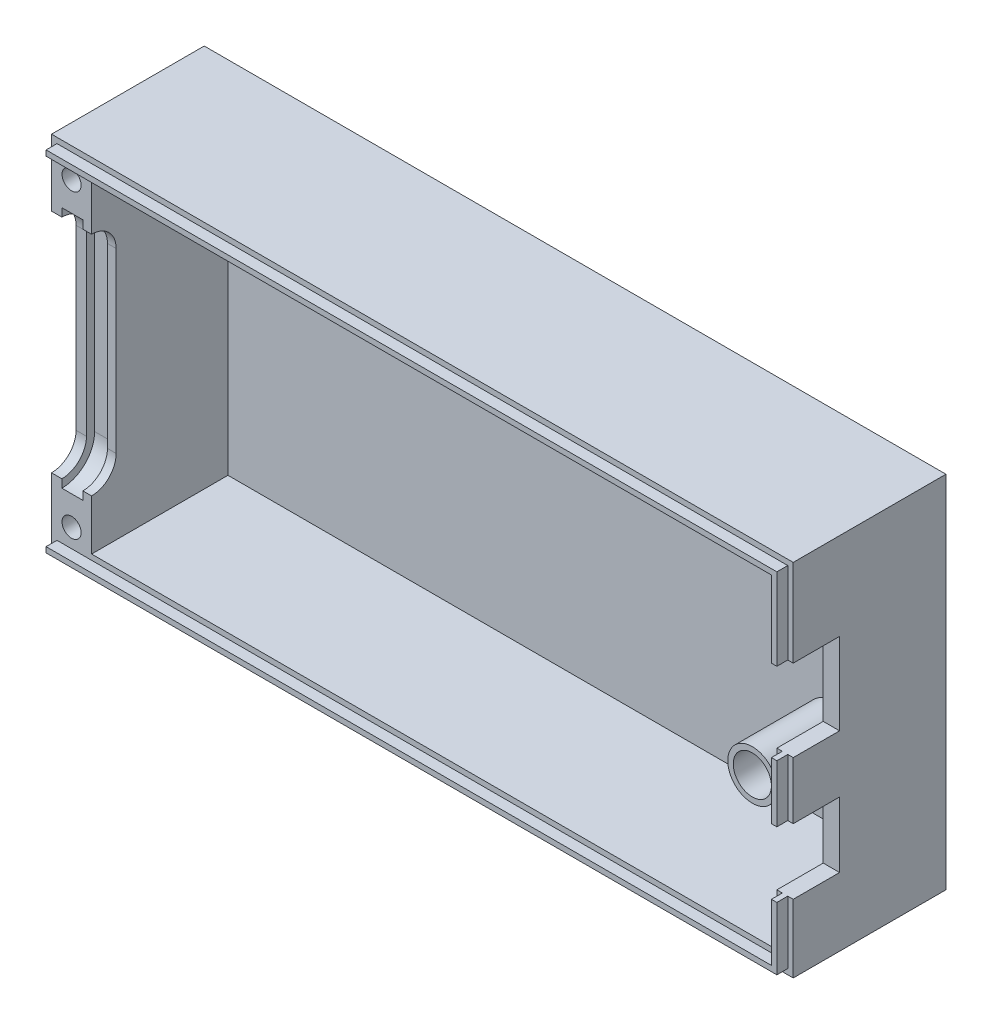
SolidWorks part; units mm, degrees
note: The reader was unsure of these and kept them because the rebuilt part matched: shared geometry of "Szkic8<2>".
ref_plane "Płaszczyzna przednia" through (0, 0, 0) normal (0, 0, 1) x (1, 0, 0)
ref_plane "Płaszczyzna górna" through (0, 0, 0) normal (0, 1, 0) x (1, 0, 0)
ref_plane "Płaszczyzna prawa" through (0, 0, 0) normal (1, 0, 0) x (0, 0, -1)
sketch "Szkic1" plane through (0, 0, 0) normal (0, 0, 1) x (1, 0, 0)
  line L1 (65, -30) -> (-65, -30)
  line L2 (65, -30) -> (65, 30)
  line L3 (65, 30) -> (-65, 30)
  line L4 (-65, -30) -> (-65, 30)
  line L5 (65, -30) -> (-65, 30) construction
  line L6 (65, 30) -> (-65, -30) construction
  point P0 (0, 0)
  dimension "D1" = 130
  dimension "D2" = 60
extrude "Dodanie-wyciągnięcie1" add sketch "Szkic1" along normal blind 25
shell "Skorupa1" thickness 3 removed face at (0, 0, 25) outward yes
sketch "Szkic3" plane through (-65, 0, 0) normal (1, 0, 0) x (0, 0, -1)
  line L4 (0, -30) -> (0, 30)
  line L5 (0, 30) -> (-25, 30)
  line L6 (-25, 30) -> (-25, -30)
  line L7 (-25, -30) -> (0, -30)
  line L8 (0, -30) -> (0, 30)
  line L9 (0, 30) -> (-25, 30)
  line L10 (-25, 30) -> (-25, -30)
  line L11 (-25, -30) -> (0, -30)
  dimension "D1" = 0
extrude "Wytnij-wyciągnięcie1" cut sketch "Szkic3" against normal blind 1.1
sketch "Szkic4" plane through (-66.1, 0, 0) normal (1, 0, 0) x (0, 0, -1)
  line L1 (-25, 30) -> (-25, -30) construction
  line L2 (-25, 30) -> (-25, -30)
  line L4 (-25, 22.175) -> (-25, -22.175)
  line L6 (-19, 16.275) -> (-19, -16.275)
  arc A2 (-19, 16.275) -> (-25, 22.275) centre (-25, 16.275) ccw
  arc A3 (-19, -16.275) -> (-25, -22.275) centre (-25, -16.275) cw
  point P1 (-25, 0)
  point P11 (-19, 0)
  dimension "D2" = 6
  dimension "D3" = 44.35
  dimension "D1" = 6
  dimension "D5" = 6
  dimension "D4" = 32.55
extrude "Dodanie-wyciągnięcie2" add sketch "Szkic4" along normal blind 3.85
sketch "Szkic5" plane through (-62.25, 0, 0) normal (1, 0, 0) x (0, 0, -1)
  line L0 (-20.5, 16.275) -> (-20.5, -16.275)
  line L1 (-25, 22.275) -> (-25, 20.775)
  line L2 (-25, -20.775) -> (-25, -22.275)
  line L6 (-19, 16.275) -> (-19, -16.275)
  line L7 (-25, -22.275) -> (-25, -30)
  line L8 (-25, -30) -> (0, -30)
  line L9 (0, -30) -> (0, 30)
  line L10 (0, 30) -> (-25, 30)
  line L11 (-25, 30) -> (-25, 22.275)
  line L12 (-19, 16.275) -> (-19, -16.275)
  line L13 (-25, -22.275) -> (-25, -30)
  line L14 (-25, -30) -> (0, -30)
  line L15 (0, -30) -> (0, 30)
  line L16 (0, 30) -> (-25, 30)
  line L17 (-25, 30) -> (-25, 22.275)
  arc A0 (-25, -20.775) -> (-20.5, -16.275) centre (-25, -16.275) ccw
  arc A1 (-20.5, 16.275) -> (-25, 20.775) centre (-25, 16.275) ccw
  arc A2 (-25, -22.275) -> (-19, -16.275) centre (-25, -16.275) ccw
  arc A3 (-25, -22.275) -> (-19, -16.275) centre (-25, -16.275) ccw
  arc A8 (-19, 16.275) -> (-25, 22.275) centre (-25, 16.275) ccw construction
  arc A9 (-25, -22.275) -> (-19, -16.275) centre (-25, -16.275) ccw construction
  arc A10 (-19, 16.275) -> (-25, 22.275) centre (-25, 16.275) ccw
  arc A11 (-19, 16.275) -> (-25, 22.275) centre (-25, 16.275) ccw
  dimension "D1" = 0
  dimension "D2" = 1.5
extrude "Dodanie-wyciągnięcie3" add sketch "Szkic5" along normal blind 1.6
sketch "Szkic6" plane through (-66.1, 0, 0) normal (1, 0, 0) x (0, 0, -1)
  line L0 (-20.5, 16.275) -> (-20.5, -16.275) construction
  line L1 (-20.5, 16.275) -> (-20.5, -16.275)
  line L3 (-25, 20.775) -> (-25, -20.775)
  arc A0 (-25, -20.775) -> (-20.5, -16.275) centre (-25, -16.275) ccw construction
  arc A1 (-20.5, 16.275) -> (-25, 20.775) centre (-25, 16.275) ccw construction
  arc A2 (-25, -20.775) -> (-20.5, -16.275) centre (-25, -16.275) ccw
  arc A3 (-20.5, 16.275) -> (-25, 20.775) centre (-25, 16.275) ccw
  dimension "D1" = 4.5
extrude "Wytnij-wyciągnięcie2" cut sketch "Szkic6" against normal through all
sketch "Szkic8" plane through (0, 0, 25) normal (0, 0, 1) x (1, 0, 0)
  line L0 (65, 30) -> (-60.65, 30) construction
  line L1 (-60.65, -30) -> (-60.65, 30) construction
  line L2 (-19.15, 25) -> (-19.15, 30)
  line L3 (65, 30) -> (-60.65, 30) construction
  line L4 (-10.15, 25) -> (-10.15, 30)
  line L5 (-68, 33) -> (-68, 20.775) construction
  line L6 (-10.15, 30) -> (-19.15, 30)
  line L8 (68, 33) -> (-68, 33) construction
  arc A0 (-19.15, 25) -> (-10.15, 25) centre (-14.65, 25) ccw
  circle A1 centre (-64.325, 27.5875) radius 1.75
  circle A2 centre (-64.325, -27.5875) radius 1.75
  circle A3 centre (-14.65, 25) radius 1.75
  point P0 (-64.325, 27.5875)
  point P5 (-64.325, -27.5875)
  point P18 (-14.65, 25)
  dimension "D4" = 9
  dimension "D7" = 3.5
  dimension "D8" = 3.5
  dimension "D9" = 3.5
  dimension "D1" = 3.675
  dimension "D2" = 5.4125
  dimension "D5" = 5
  dimension "D6" = 46
  dimension "D3" = 2
extrude "Dodanie-wyciągnięcie4" add sketch "Szkic8" against normal up to surface (25 mm away) up to face at (2.175, 0, 0)
extrude "Wytnij-wyciągnięcie3" cut sketch "Szkic8<2>" against normal blind 10 contours A1 | A2
sketch "Szkic8<2>" plane through (0, 0, 25) normal (0, 0, 1) x (1, 0, 0) same geometry as "Szkic8"
sketch "Szkic9" plane through (0, 0, 0) normal (0, 0, 1) x (1, 0, 0)
  circle A1 centre (-14.65, 25) radius 1.75
  circle A2 centre (-14.65, 25) radius 1.75
  dimension "D1" = 0
extrude "Dodanie-wyciągnięcie5" add sketch "Szkic9" along normal blind 5
sketch "Szkic10" plane through (0, 0, 25) normal (0, 0, 1) x (1, 0, 0)
  line L0 (-61.65, 31) -> (-67, 31)
  line L1 (-67, 32) -> (-67, 31)
  line L2 (-11.15, 31) -> (-18.15, 31)
  line L3 (-61.65, -31) -> (-67, -31)
  line L4 (-67, -31) -> (-67, -32)
  line L33 (-67, 23.275) -> (-61.65, 23.275)
  line L35 (-61.65, -23.275) -> (-67, -23.275)
  line L60 (-61.65, 23.275) -> (-61.65, 31)
  line L75 (-61.65, 31) -> (-18.15, 31)
  line L76 (-18.15, 31) -> (-18.15, 25)
  line L77 (-11.15, 25) -> (-11.15, 31)
  line L78 (-11.15, 31) -> (66, 31)
  line L79 (66, 31) -> (66, -31)
  line L80 (66, -31) -> (-61.65, -31)
  line L81 (-61.65, -31) -> (-61.65, -23.275)
  line L83 (-67, -23.275) -> (-67, -32)
  line L84 (-67, -32) -> (67, -32)
  line L85 (67, -32) -> (67, 32)
  line L86 (67, 32) -> (-67, 32)
  line L87 (-67, 32) -> (-67, 23.275)
  line L90 (-61.65, 31) -> (-18.15, 31)
  line L93 (-11.15, 31) -> (66, 31)
  line L94 (66, 31) -> (66, -31)
  line L95 (66, -31) -> (-61.65, -31)
  line L99 (-67, -32) -> (67, -32)
  line L100 (67, -32) -> (67, 32)
  line L101 (67, 32) -> (-67, 32)
  arc A2 (-18.15, 25) -> (-11.15, 25) centre (-14.65, 25) ccw
  dimension "D1" = 1
extrude "Dodanie-wyciągnięcie6" add sketch "Szkic10" along normal blind 2
sketch "Szkic11" plane through (0, 0, 25) normal (0, 0, 1) x (1, 0, 0)
  line L1 (-19.15, 30) -> (-10.15, 30)
  line L2 (-19.15, 30) -> (-19.15, 20.5)
  line L3 (-19.15, 20.5) -> (-10.15, 20.5)
  line L4 (-10.15, 30) -> (-10.15, 20.5)
extrude "Wytnij-wyciągnięcie4" cut sketch "Szkic11" against normal offset from surface (10.5 mm away) 6 up to face at (-67.05, 0, 20.5)
sketch "Szkic14" plane through (0, 0, 14.5) normal (0, 0, 1) x (1, 0, 0)
  line L0 (-10.15, 30) -> (68, 30) construction
  line L1 (68, -33) -> (68, 33) construction
  line L2 (68, 30) -> (68, -28.2321) construction
sketch "Szkic15" plane through (68, 0, 0) normal (1, 0, 0) x (0, 0, -1)
  line L0 (-14.5, 30) -> (-14.5, -28.2321) construction
  line L1 (-14.5, 30) -> (-14.5, -28.2321) construction
  line L2 (-31.5, -20.5) -> (-16.5, -20.5)
  line L3 (-31.5, -20.5) -> (-31.5, -8.5)
  line L4 (-25, -33) -> (3, -33) construction
  line L5 (-16.5, -20.5) -> (-16.5, -8.5)
  line L6 (-16.5, -8.5) -> (-31.5, -8.5)
  line L7 (-31.5, 2) -> (-16.5, 2)
  line L8 (-31.5, 2) -> (-31.5, 17)
  line L9 (-31.5, 17) -> (-16.5, 17)
  line L10 (-16.5, 17) -> (-16.5, 2)
  point P5 (-24, -8.5)
  dimension "D1" = 12
  dimension "D2" = 15
  dimension "D3" = 2
  dimension "D4" = 12.5
  dimension "D5" = 10.5
  dimension "D6" = 15
  dimension "D7" = 15
  dimension "D8" = 2
extrude "Wytnij-wyciągnięcie5" cut sketch "Szkic15" against normal up to next
sketch "Szkic16" plane through (-68, 0, 0) normal (-1, 0, 0) x (0, 0, 1)
  line L0 (25, 33) -> (-3, 33) construction
  line L2 (-3, 33) -> (-3, -33) construction
  circle A0 centre (5, 25) radius 3.5
  dimension "D1" = 7
  dimension "D2" = 8
  dimension "D3" = 8
extrude "Wytnij-wyciągnięcie6" cut sketch "Szkic16" against normal up to surface (7.35 mm away) up to face at (-60.65, 0, 17.392)
sketch "Szkic17" plane through (0, 0, 0) normal (0, 0, 1) x (1, 0, 0)
  line L0 (50, -15) -> (65, -15) construction
  line L1 (65, -30) -> (65, 30) construction
  line L2 (50, -15) -> (50, -30) construction
  line L3 (-60.65, -30) -> (65, -30) construction
  line L4 (55, 27) -> (55, 30) construction
  line L5 (65, 30) -> (-60.65, 30) construction
  line L6 (55, 27) -> (65, 27) construction
  line L7 (65, 17) -> (65, 30) construction
  line L8 (52, 27) -> (52, 30)
  line L9 (58, 27) -> (58, 30)
  line L10 (52, 30) -> (58, 30)
  circle A0 centre (50, -15) radius 4.5
  circle A1 centre (50, -15) radius 3.5
  circle A2 centre (55, 27) radius 1.75
  arc A3 (52, 27) -> (58, 27) centre (55, 27) ccw
  dimension "D1" = 15
  dimension "D3" = 9
  dimension "D4" = 7
  dimension "D7" = 3.5
  dimension "D8" = 6
  dimension "D2" = 15
  dimension "D5" = 10
  dimension "D6" = 3
extrude "Dodanie-wyciągnięcie7" add sketch "Szkic17" along normal up to surface (14.5 mm away) up to face at (-14.65, 26.375, 14.5)
